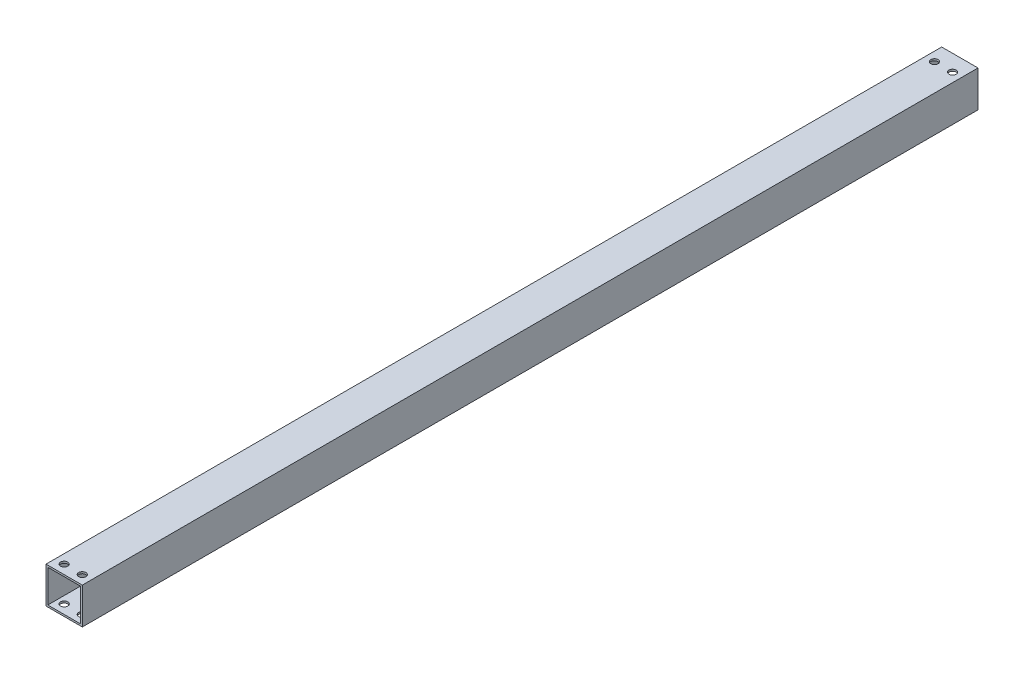
SolidWorks part; units mm, degrees
ref_plane "前视基准面" through (0, 0, 0) normal (0, 0, 1) x (1, 0, 0)
ref_plane "上视基准面" through (0, 0, 0) normal (0, 1, 0) x (1, 0, 0)
ref_plane "右视基准面" through (0, 0, 0) normal (1, 0, 0) x (0, 0, -1)
other "Configuration Table"
sketch "草图1" plane through (0, 0, 0) normal (0, 0, 1) x (1, 0, 0)
  line L0 (-9, 9) -> (-9, -9)
  line L1 (-10, 10) -> (10, 10)
  line L2 (-10, 10) -> (-10, -10)
  line L3 (-10, -10) -> (10, -10)
  line L4 (10, 10) -> (10, -10)
  line L5 (-10, 10) -> (10, -10) construction
  line L6 (-10, -10) -> (10, 10) construction
  line L7 (-9, -9) -> (9, -9)
  line L8 (9, 9) -> (9, -9)
  line L9 (-9, 9) -> (9, 9)
  point P0 (0, 0)
  dimension "D1" = 20
  dimension "D2" = 20
  dimension "D3" = 1
extrude "凸台-拉伸1" add sketch "草图1" along normal blind 493.33
sketch "草图5" plane through (0, 9, 0) normal (0, -1, 0) x (1, 0, 0)
  circle A4 centre (-5, 9) radius 2
  circle A5 centre (5, 9) radius 2
extrude "切除-拉伸12" cut sketch "草图5" against normal blind 20 contours A4 | A5
sketch "草图6" plane through (0, -9, 0) normal (0, 1, 0) x (1, 0, 0)
  circle A0 centre (5, -9) radius 2 construction
  circle A1 centre (5, -9) radius 2
  circle A2 centre (-5, -9) radius 2 construction
  circle A3 centre (-5, -9) radius 2
  circle A4 centre (293.56, -9) radius 2 construction
  circle A5 centre (303.56, -9) radius 2 construction
  circle A6 centre (293.56, -9) radius 2
  circle A7 centre (303.56, -9) radius 2
  circle A8 centre (15.3942, -478.33) radius 2 construction
  circle A9 centre (15.3942, -488.33) radius 2
  circle A10 centre (15.3942, -488.33) radius 2
  circle A11 centre (-5, -488.33) radius 2 construction
  circle A12 centre (5, -488.33) radius 2 construction
  circle A13 centre (15.3942, -478.33) radius 2
  circle A14 centre (-5, -488.33) radius 2
  circle A15 centre (5, -488.33) radius 2
  circle A16 centre (15.3942, -488.33) radius 2 construction
  circle A17 centre (15.3942, -478.33) radius 2
  circle A18 centre (15.3942, -488.33) radius 2
  circle A19 centre (5, -488.33) radius 2
  circle A20 centre (-5, -488.33) radius 2
  circle A21 centre (303.56, -488.33) radius 2 construction
  circle A22 centre (293.56, -488.33) radius 2 construction
  circle A23 centre (283.56, -488.33) radius 2 construction
  circle A24 centre (283.56, -478.33) radius 2 construction
  circle A25 centre (303.56, -488.33) radius 2
  circle A26 centre (293.56, -488.33) radius 2
  circle A27 centre (283.56, -488.33) radius 2
  circle A28 centre (283.56, -478.33) radius 2
  dimension "D1" = 0
extrude "切除-拉伸13" cut sketch "草图6" against normal blind 84 and the other way blind 146 contours A7 | A1 | A3 | A13 | A10 | A15 | A14 | A27 | A28 | A26 | A25 | A6 region at (5, -9, 9) region at (-5, -9, 9) region at (303.56, -9, 9) region at (15.3942, -9, 488.33) region at (15.3942, -9, 478.33) region at (-5, -9, 488.33) region at (5, -9, 488.33) region at (303.56, -9, 488.33) region at (293.56, -9, 488.33) region at (283.56, -9, 488.33) region at (283.56, -9, 478.33)
